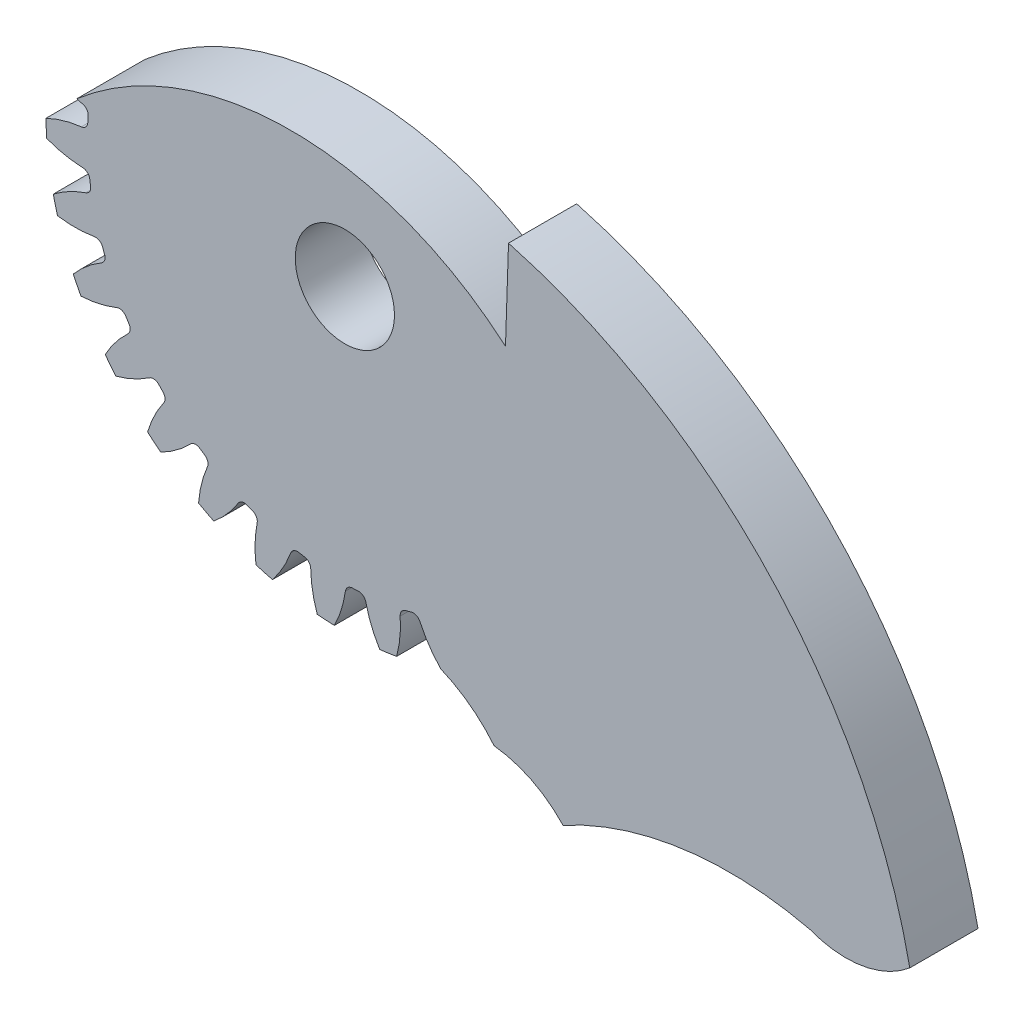
SolidWorks part; units mm, degrees
ref_plane "Front" through (0, 0, 0) normal (0, 0, 1) x (1, 0, 0)
ref_plane "Top" through (0, 0, 0) normal (0, 1, 0) x (1, 0, 0)
ref_plane "Right" through (0, 0, 0) normal (1, 0, 0) x (0, 0, -1)
sketch "Sketch3" plane through (0, 0, 0) normal (0, 0, 1) x (1, 0, 0)
  circle A0 centre (0, 0) radius 40.64
  dimension "od" = 81.28
extrude "gearBody" add sketch "Sketch3" along normal blind 25.4
sketch "Sketch2" plane through (0, 0, 0) normal (0, 0, 1) x (1, 0, 0)
  line L0 (0, 0) -> (34.0786, 14.1158) construction
  line L1 (45.4751, -11.4855) -> (0, 0) construction
  line L2 (0, 0) -> (36.3143, 0) construction
  line L3 (38.0972, -0.458) -> (37.8451, -4.4001) construction
  line L5 (37.9712, -2.4291) -> (0, 0) construction
  line L7 (0, 0) -> (36.8864, 0) construction
  arc A0 (36.879, -0.7403) -> (36.6727, -3.9649) centre (0, 0) ccw construction
  arc A1 (40.637, 0.4947) -> (40.2427, -5.6687) centre (0, 0) ccw construction
  arc A2 (38.0972, -0.458) -> (37.8451, -4.4001) centre (0, 0) ccw construction
  arc A3 (34.9015, -2.6404) -> (34.9534, -1.8283) centre (0, 0) ccw
  arc A4 (45.4751, -11.4855) -> (35.6466, -3.6712) centre (32.0022, -18.3431) ccw
  arc A5 (45.4751, -11.4855) -> (46.5679, 5.5974) centre (0, 0) ccw
  arc A6 (46.5679, 5.5974) -> (35.8238, -0.9008) centre (34.0786, 14.1158) cw
  arc A7 (34.9534, -1.8283) -> (35.8238, -0.9008) centre (35.9376, -1.8798) cw
  arc A8 (35.6466, -3.6712) -> (34.9015, -2.6404) centre (35.8842, -2.7147) cw
  point P6 (46.5679, 5.5974)
  point P22 (45.4751, -11.4855)
  dimension "baseDia" = 73.7729
  dimension "od" = 81.28
  dimension "pd" = 76.2
  dimension "rd" = 70.0024
  dimension "rFillet" = 0.9855
  dimension "pointX" = 46.5679
  dimension "pointY" = 5.5974
  dimension "CTT" = 3.9421
  dimension "flankCenterAngle" = 22.5
extrude "toothCut" cut sketch "Sketch2" along normal through all
pattern_circular "CirPattern1" count 30 over 360 about axis through (0, 0, 25.4) along (0, 0, -1) of "toothCut"
sketch "hub1Dia" plane through (0, 0, 0) normal (0, 0, -1) x (-1, 0, 0)
  circle A0 centre (0, 0) radius 12.7
  dimension "hub1Dia" = 25.4
sketch "hub2Dia" plane through (0, 0, 25.4) normal (0, 0, 1) x (1, 0, 0)
  circle A0 centre (0, 0) radius 12.7
  dimension "hub2dia" = 25.4
sketch "boreDia" plane through (0, 0, 0) normal (0, 0, 1) x (1, 0, 0)
  circle A0 centre (0, 0) radius 9.525
  dimension "boreDia" = 19.05
extrude "bore" cut sketch "boreDia" against normal mid plane 25400
sketch "Sketch4" plane through (0, 0, 25.4) normal (0, 0, 1) x (1, 0, 0)
  circle A0 centre (1.8913, -57.4779) radius 76.1746
  arc A1 (46.3822, 4.3535) -> (-43.5544, 3.6553) centre (1.4277, 2.2323) ccw
  point P6 (0, 0)
  point P7 (0, 0)
  point P8 (0, 0)
  point P9 (0, 0)
  dimension "D1" = 152.3492
extrude "Cut-Extrude1" cut sketch "Sketch4" against normal through all contours A0 A1 region at (1.2313, 27.5308, 25.4)
sketch "Sketch5" plane through (0, 0, 25.4) normal (0, 0, 1) x (1, 0, 0)
  line L0 (-40.5204, 5.7978) -> (17.7171, 12.4887)
  line L1 (17.7171, 12.4887) -> (8.9608, -26.928)
  line L2 (8.9608, -26.928) -> (13.028, -38.4952)
  arc A2 (13.028, -38.4952) -> (24.1586, -52.1288) centre (5.7938, -55.7616) cw
  arc A3 (63.24, -44.0814) -> (24.1586, -52.1288) centre (52.353, -90.1309) ccw
  arc A7 (76.8188, -41.8196) -> (-40.5204, 5.7978) centre (2.2241, -57.2535) ccw
  arc A8 (63.24, -44.0814) -> (76.8188, -41.8196) centre (68.1274, -31.5314) ccw
  arc A9 (32.8322, 12.1298) -> (-33.5657, 9.9415) centre (1.8913, -57.4779) ccw construction
  point P2 (39.7811, 9.019)
  point P4 (0, 0)
  point P5 (0, 0)
  point P10 (76.8188, -41.8196)
  point P16 (32.3965, 12.6907)
  point P17 (-10.2393, 17.7246)
  point P21 (13.028, 13.0594)
  point P22 (10.8956, -32.4306)
  point P23 (24.8679, 8.3649)
  point P24 (17.7171, 12.4887)
  dimension "D2" = 152.3492
extrude "Boss-Extrude1" add sketch "Sketch5" against normal up to surface (25.4 mm away) up to face at (9.525, 0, 0)
sketch "Sketch6" plane through (0, 0, 0) normal (0, 1, 0) x (1, 0, 0)
  line L0 (-46.1384, -9.271) -> (97.8162, -9.271)
  line L4 (97.8162, -9.271) -> (71.9328, -41.1538)
  line L5 (71.9328, -41.1538) -> (-48.6783, -38.0647)
  line L6 (-48.6783, -38.0647) -> (-46.1384, -9.271)
  dimension "D1" = 9.271
extrude "Cut-Extrude2" cut sketch "Sketch6" against normal through all both and the other way through all
sketch "Sketch7" plane through (0, 0, 9.271) normal (0, 0, 1) x (1, 0, 0)
  line L0 (21.8411, 3.894) -> (22.2513, 16.2413)
  line L1 (-36.4485, 3.894) -> (-43.5776, 3.303)
  line L2 (-43.5776, 3.303) -> (-36.8766, 21.2616)
  line L3 (-36.8766, 21.2616) -> (23.9011, 23.2048)
  line L4 (23.9011, 23.2048) -> (22.2513, 16.2413)
  arc A0 (-40.2427, 5.6687) -> (-35.6466, 3.6712) centre (-32.0022, 18.3431) ccw construction
  arc A1 (76.8188, -41.8196) -> (-40.5204, 5.7978) centre (2.2241, -57.2535) ccw construction
  arc A2 (-36.4485, 3.894) -> (21.8411, 3.894) centre (-7.3037, -29.8805) cw
  point P0 (-36.4485, 3.894)
  point P1 (-5.3442, 14.9882)
  point P5 (21.8411, 3.894)
  point P6 (21.4449, 16.4563)
  point P7 (21.8411, 14.3516)
  point P11 (22.2513, 12.4032)
  point P12 (22.2513, 10.6257)
  point P13 (21.8411, 9.0875)
  point P14 (21.8411, 7.4467)
  point P15 (21.8411, 5.8743)
extrude "Cut-Extrude3" cut sketch "Sketch7" against normal through all both
sketch "Sketch8" plane through (0, 0, 9.271) normal (0, 0, 1) x (1, 0, 0)
  circle A0 centre (0, 0) radius 6.7469
  circle A1 centre (0, 0) radius 10.9012
  dimension "D1" = 13.4937
extrude "Boss-Extrude2" add sketch "Sketch8" against normal up to surface (9.271 mm away) up to face at (-14.6896, -23.323, 0)
sketch "Sketch9" plane through (0, 0, 9.271) normal (0, 0, 1) x (1, 0, 0)
  line L0 (20.2954, -43.9224) -> (23.1683, -52.6945)
  line L1 (23.1683, -52.6945) -> (26.5794, -52.804)
  line L2 (26.5794, -52.804) -> (29.6611, -48.6079)
  arc A0 (24.1586, -52.1288) -> (13.028, -38.4952) centre (5.7938, -55.7616) ccw construction
  arc A1 (63.24, -44.0814) -> (24.1586, -52.1288) centre (52.353, -90.1309) ccw construction
  arc A2 (20.2954, -43.9224) -> (29.6611, -48.6079) centre (18.6746, -58.8652) cw
  point P0 (27.8575, -49.0551)
  point P1 (25.2947, -45.6047)
  point P2 (22.4218, -43.2707)
  point P3 (19.1914, -41.3058)
  point P4 (20.2954, -43.9224)
  point P5 (29.6611, -48.6079)
extrude "Cut-Extrude4" cut sketch "Sketch9" against normal through all both
